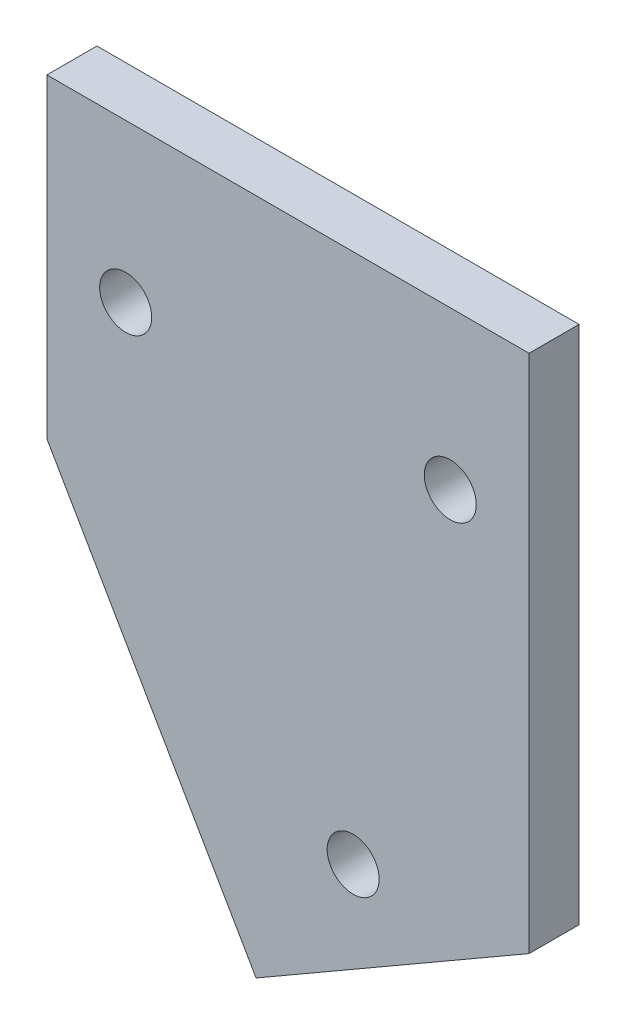
SolidWorks part; units mm, degrees
ref_plane "Front Plane" through (0, 0, 0) normal (0, 0, 1) x (1, 0, 0)
ref_plane "Top Plane" through (0, 0, 0) normal (0, 1, 0) x (1, 0, 0)
ref_plane "Right Plane" through (0, 0, 0) normal (1, 0, 0) x (0, 0, -1)
sketch "Sketch1" plane through (0, 0, 0) normal (0, 0, 1) x (1, 0, 0)
  line L0 (0, 0) -> (13.2735, -22.9904)
  line L1 (13.2735, -22.9904) -> (30.594, -12.9904)
  line L2 (30.594, -12.9904) -> (30.594, 20)
  line L3 (30.594, 20) -> (0, 20)
  line L4 (0, 20) -> (0, 0)
  line L5 (0, 0) -> (30.594, 0) construction
  line L6 (30.594, -12.9904) -> (23.094, 0) construction
  line L7 (0, 10) -> (30.594, 10) construction
  line L8 (21.9338, -17.9904) -> (19.4338, -13.6603) construction
  circle A0 centre (19.4338, -13.6603) radius 1.65
  circle A1 centre (5, 10) radius 1.65
  circle A2 centre (25.594, 10) radius 1.65
  point P16 (20.8757, -36.1578)
  point P17 (25.6939, -24.5031)
  point P19 (15.6084, -7.0346)
  point P20 (12.6546, -21.9184)
  point P21 (25.5866, 10)
  point P22 (14.8857, -25.7828)
  point P23 (18.5889, -12.1969)
  point P24 (14.2113, -24.6148)
  dimension "D3" = 3.3
  dimension "D1" = 20
  dimension "D2" = 30
  dimension "D4" = 5
  dimension "D5" = 5
  dimension "D6" = 5
  dimension "D7" = 15
extrude "Boss-Extrude1" add sketch "Sketch1" along normal blind 3.175
